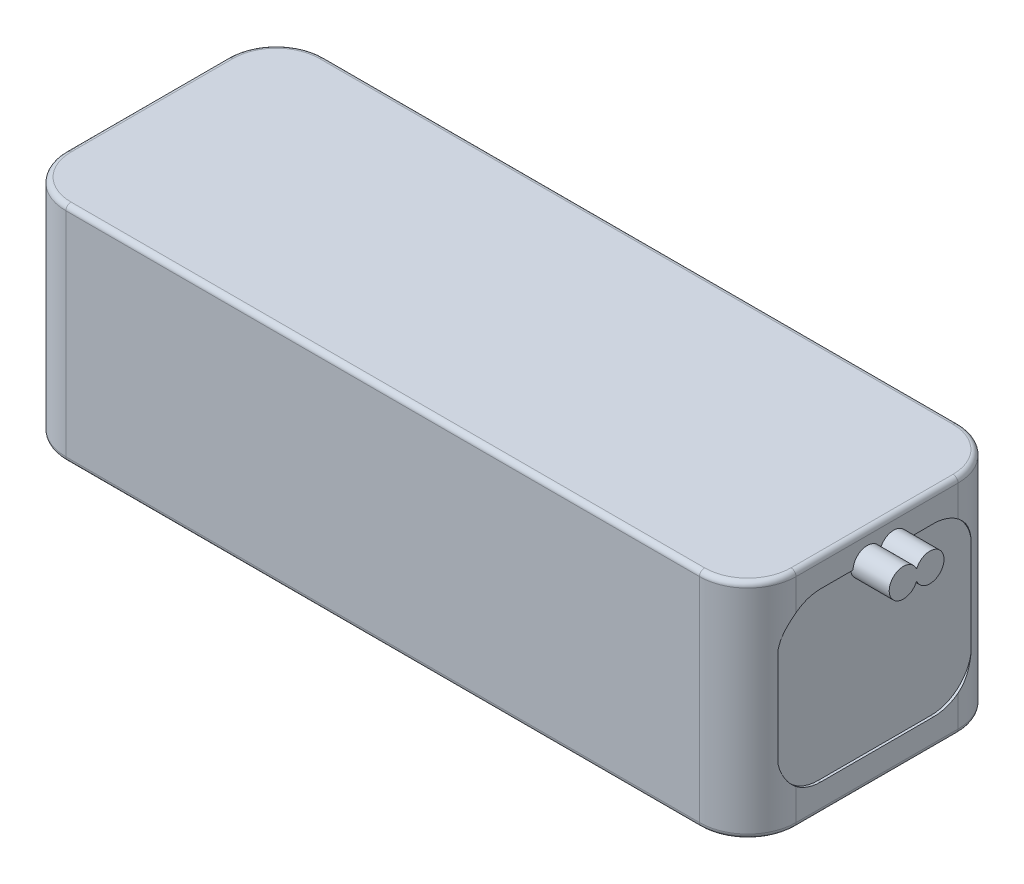
SolidWorks part; units mm, degrees
ref_plane "Front Plane" through (0, 0, 0) normal (0, 0, 1) x (1, 0, 0)
ref_plane "Top Plane" through (0, 0, 0) normal (0, 1, 0) x (1, 0, 0)
ref_plane "Right Plane" through (0, 0, 0) normal (1, 0, 0) x (0, 0, -1)
ref_plane "Plane1" through (0, 0, -15) normal (0, 0, -1) x (-1, 0, 0)
sketch "Sketch1" plane through (0, 0, -15) normal (0, 0, -1) x (-1, 0, 0)
  line L0 (-69, -22) -> (75, -22)
  line L1 (75, -22) -> (75, 22)
  line L2 (75, 22) -> (-69, 22)
  line L3 (-69, 22) -> (-69, -22)
  line L4 (-69, 0) -> (75, 0) construction
  line L5 (3, 22) -> (3, -22) construction
  dimension "D1" = 44
  dimension "D2" = 144
extrude "Boss-Extrude1" add sketch "Sketch1" against normal blind 51
sketch "Sketch2" plane through (69, 0, 0) normal (1, 0, 0) x (0, 0, -1)
  line L0 (-29.625, 8.5) -> (-29.625, -8.5)
  line L1 (-21.625, -16.5) -> (0.625, -16.5)
  line L2 (8.625, -8.5) -> (8.625, 8.5)
  line L3 (0.625, 16.5) -> (-21.625, 16.5)
  line L4 (-36, 22) -> (15, -22) construction
  line L5 (15, 22) -> (-36, -22) construction
  line L6 (-29.625, 16.5) -> (8.625, -16.5) construction
  line L7 (8.625, 16.5) -> (-29.625, -16.5) construction
  line L12 (-36, 22) -> (15, 22) construction
  line L13 (-36, 22) -> (-36, -22) construction
  line L14 (-36, -22) -> (15, -22) construction
  line L15 (15, 22) -> (15, -22) construction
  line L16 (-36, 22) -> (15, -22) construction
  line L17 (-36, -22) -> (15, 22) construction
  arc A0 (-29.625, -8.5) -> (-21.625, -16.5) centre (-21.625, -8.5) ccw
  arc A1 (0.625, -16.5) -> (8.625, -8.5) centre (0.625, -8.5) ccw
  arc A2 (8.625, 8.5) -> (0.625, 16.5) centre (0.625, 8.5) ccw
  arc A3 (-29.625, 8.5) -> (-21.625, 16.5) centre (-21.625, 8.5) cw
  point P16 (-10.5, 0)
  dimension "D1" = 38.25
  dimension "D2" = 51
  dimension "D3" = 8
extrude "Cut-Extrude1" cut sketch "Sketch2" against normal blind 0.5
sketch "Sketch3" plane through (-75, 0, 0) normal (-1, 0, 0) x (0, 0, 1)
  line L0 (18.195, 16.5) -> (2.805, 16.5)
  line L1 (-8.625, 5.07) -> (-8.625, -5.07)
  line L2 (2.805, -16.5) -> (18.195, -16.5)
  line L3 (29.625, -5.07) -> (29.625, 5.07)
  line L4 (-8.625, 16.5) -> (29.625, -16.5) construction
  line L5 (29.625, 16.5) -> (-8.625, -16.5) construction
  line L6 (-15, 22) -> (36, -22) construction
  line L7 (36, -22) -> (-15, -22) construction
  line L8 (-15, -22) -> (36, 22) construction
  arc A0 (-8.625, -5.07) -> (2.805, -16.5) centre (2.805, -5.07) ccw
  arc A1 (18.195, -16.5) -> (29.625, -5.07) centre (18.195, -5.07) ccw
  arc A2 (18.195, 16.5) -> (29.625, 5.07) centre (18.195, 5.07) cw
  arc A3 (2.805, 16.5) -> (-8.625, 5.07) centre (2.805, 5.07) ccw
  dimension "D3" = 11.43
  dimension "D1" = 38.25
  dimension "D2" = 51
extrude "Cut-Extrude2" cut sketch "Sketch3" against normal blind 0.5
fillet "Fillet1" radius 9.525 4 edges at (-75, 0, -15) (-75, 0, 36) (69, 0, -15) (69, 0, 36) tangent propagation no
fillet "Fillet2" radius 1 16 edges at (66.2102, 22, -12.2102) (69, 22, 10.5) (-3, 22, -15) (66.2102, 22, 33.2102) (-72.2102, 22, -12.2102) (-3, 22, 36) (-75, 22, 10.5) (-72.2102, 22, 33.2102) (-75, -22, 10.5) (-72.2102, -22, -12.2102) (-72.2102, -22, 33.2102) (-3, -22, -15) (-3, -22, 36) (66.2102, -22, -12.2102) (66.2102, -22, 33.2102) (69, -22, 10.5) tangent propagation no
sketch "Sketch4" plane through (0, 0, 36) normal (0, 0, 1) x (1, 0, 0)
  line L0 (-65.475, 0) -> (59.475, 0) construction
  line L1 (-65.475, 21) -> (-65.475, -21) construction
  line L2 (59.475, -21) -> (59.475, 21) construction
  line L3 (-3, 25.9735) -> (-3, -21) construction
  line L4 (-65.475, -21) -> (59.475, -21) construction
  circle A0 centre (-3, 0) radius 0.5026
sketch "Sketch5" plane through (68.5, 0, 0) normal (1, 0, 0) x (0, 0, -1)
  line L0 (0.625, 16.5) -> (-21.625, 16.5) construction
  line L1 (0.625, 16.5) -> (-21.625, 16.5) construction
  circle A0 centre (-12.4391, 16.5) radius 2.794
  circle A1 centre (-7.2257, 16.5) radius 2.794
  line M4 (0.625, 16.5) -> (-21.625, 16.5)
  dimension "D1" = 5.588
extrude "Boss-Extrude2" add sketch "Sketch5" along normal blind 7.62 and the other way blind 2.54 contours A1 A0 M4 | A1 A0 M4 | A1 A0 M4 | A0 A1 M4 | A1 A0 M4 | A0 A1 M4 region at (68.5, 16.8789, 9.8324) region at (68.5, 15.2972, 7.1708) region at (68.5, 17.7028, 7.1708) region at (68.5, 16.1211, 9.8324) region at (68.5, 17.7028, 12.494) region at (68.5, 15.2972, 12.494)
equation "\"D1@Sketch3\"=\"D2@Sketch3\" * .75"
equation "\"D1@Sketch2\"=\"D2@Sketch2\"* .75"
